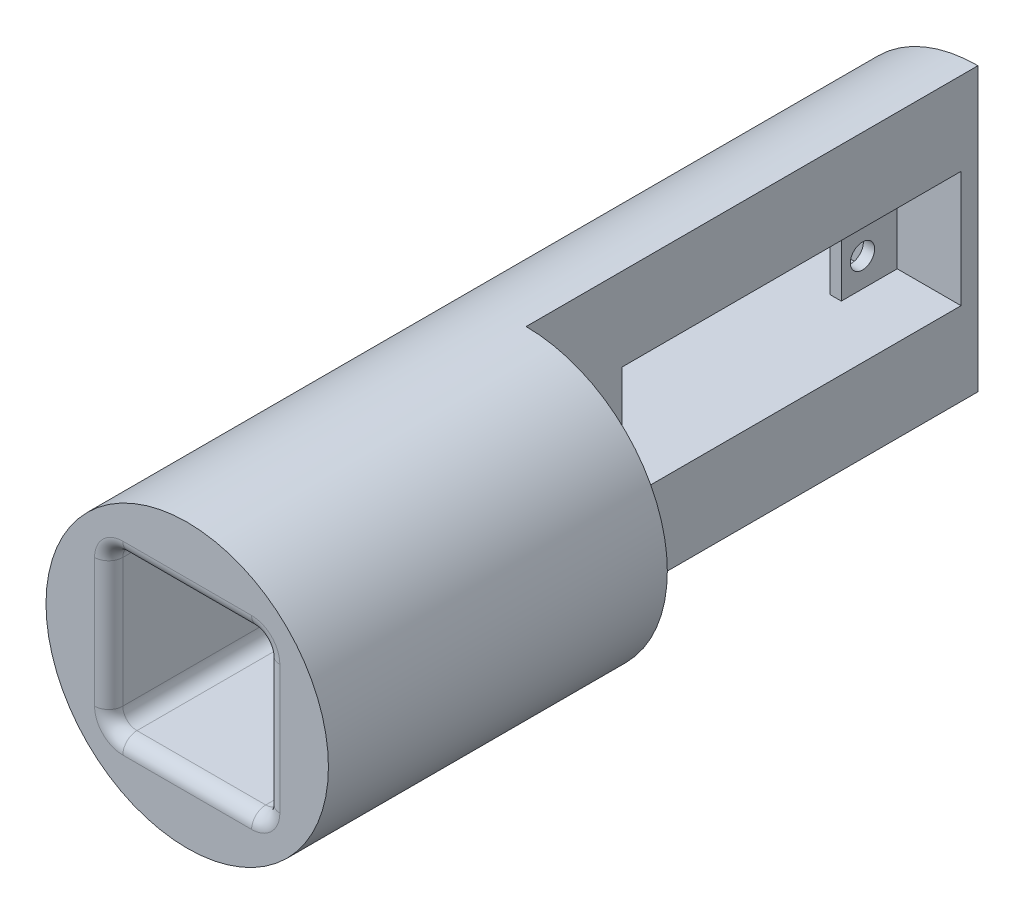
SolidWorks part; units mm, degrees
material "Custom Plastic"
ref_plane "Front Plane" through (0, 0, 0) normal (0, 0, 1) x (1, 0, 0)
ref_plane "Top Plane" through (0, 0, 0) normal (0, 1, 0) x (1, 0, 0)
ref_plane "Right Plane" through (0, 0, 0) normal (1, 0, 0) x (0, 0, -1)
sketch "Sketch1" plane through (0, 0, 0) normal (0, 0, 1) x (1, 0, 0)
  line L0 (-13.9, 13.9) -> (13.9, -13.9) construction
  line L1 (-13.9, 13.9) -> (13.9, 13.9)
  line L2 (-13.9, 13.9) -> (-13.9, -13.9)
  line L3 (-13.9, -13.9) -> (13.9, -13.9)
  line L4 (13.9, 13.9) -> (13.9, -13.9)
  circle A0 centre (0, 0) radius 25
  point P7 (0, 0)
  dimension "D2" = 50
  dimension "2.75" = 27.8
extrude "Boss-Extrude1" add sketch "Sketch1" along normal blind 55
sketch "Sketch2" plane through (0, 0, 0) normal (0, 0, -1) x (-1, 0, 0)
  circle A0 centre (0, 0) radius 25
  circle A1 centre (0, 0) radius 25
  circle A2 centre (0, 0) radius 25
  circle M2 centre (0, 0) radius 25
  line M3 (13.9, 13.9) -> (13.9, -13.9)
  line M4 (13.9, -13.9) -> (-13.9, -13.9)
  line M5 (-13.9, -13.9) -> (-13.9, 13.9)
  line M6 (-13.9, 13.9) -> (13.9, 13.9)
  dimension "D1" = 0
extrude "Boss-Extrude2" add sketch "Sketch2" along normal blind 5 contours M2 M6 M3 M4 M5 | M3 M6 M5 M4 region at (24.2929, 0, 0) region at (0, 0, 0)
sketch "Sketch3" plane through (0, 0, -5) normal (0, 0, -1) x (-1, 0, 0)
  line L1 (0, 25) -> (25, 25)
  line L2 (0, 25) -> (0, -25)
  line L3 (0, -25) -> (25, -25)
  line L4 (25, 25) -> (25, -25)
  circle A0 centre (0, 0) radius 25 construction
extrude "Boss-Extrude3" add sketch "Sketch3" along normal blind 80
ref_plane "Plane1" through (0, 0, -5) normal (0, 0, 1) x (1, 0, 0)
fillet "Fillet1" radius 2.5 4 edges at (-13.9, 13.9, 27.5) (13.9, 13.9, 27.5) (-13.9, -13.9, 27.5) (13.9, -13.9, 27.5)
fillet "Fillet2" radius 2.5 1 edges at (13.9, 0, 55) type face fillet first side face at (25, 0, 55) second side face at (13.9, 0, 27.5)
ref_plane "Plane2" through (-50, 0, 0) normal (-1, 0, 0) x (0, 0, 1)
sketch "Sketch18" plane through (0, 0, -5) normal (0, 0, 1) x (1, 0, 0)
  line L0 (0, -25) -> (-25, -25)
  line L1 (-25, 0) -> (-25, 25)
  line L2 (-25, -25) -> (0, -25)
  line L3 (-25, 0) -> (-25, -25)
  line L4 (-25, -25) -> (0, -25)
  line L5 (-25, 0) -> (-25, -25)
  line L6 (-25, 25) -> (0, 25)
  arc A1 (-25, 0) -> (0, -25) centre (0, 0) ccw
  arc A2 (-25, 0) -> (0, -25) centre (0, 0) ccw
  circle A3 centre (0, 0) radius 25
  circle A4 centre (0, 0) radius 25
  line M5 (-25, 25) -> (-25, 0)
  arc M6 (-25, 0) -> (0, 25) centre (0, 0) cw
  line M7 (0, 25) -> (-25, 25)
  dimension "D1" = 0
  dimension "D2" = 0
sketch "Sketch21" plane through (0, 0, 0) normal (1, 0, 0) x (0, 0, -1)
  line L0 (22, 10.3) -> (82, 10.3)
  line L1 (82, 10.3) -> (82, -10.3)
  line L2 (82, -10.3) -> (22, -10.3)
  line L3 (22, -10.3) -> (22, 10.3)
  line L6 (85, 25) -> (85, -25) construction
  line L7 (52, -10.3) -> (52, -25)
  line L8 (85, -25) -> (5, -25) construction
  line L9 (52, 10.3) -> (52, 25)
  line L10 (85, 25) -> (5, 25) construction
  dimension "D1" = 3
  dimension "D2" = 60
  dimension "D3" = 20.6
extrude "Cut-Extrude1" cut sketch "Sketch21" against normal blind 11.3 contours L3 L0 L1 L2
sketch "Sketch22" plane through (0, 0, 0) normal (1, 0, 0) x (0, 0, -1)
  line L0 (31.6, 10.3) -> (72.1, 10.3)
  line L1 (22, 10.3) -> (82, 10.3) construction
  line L2 (72.1, 10.3) -> (72.1, -10.3)
  line L4 (72.1, -10.3) -> (31.6, -10.3)
  line L5 (31.6, 10.3) -> (31.6, -10.3)
  line L6 (85, 25) -> (85, -25) construction
  line M9 (82, -10.3) -> (22, -10.3)
  line M11 (22, 10.3) -> (82, 10.3)
  dimension "D1" = 40.5
  dimension "D2" = 12.9
  dimension "D3" = 20.6
extrude "Cut-Extrude2" cut sketch "Sketch22" against normal through all contours L5 L2 M11 M9 region at (0, 0, -51.85)
extrude "Cut-Extrude3" cut sketch "Sketch18" against normal through all contours A2 L5 L0 | M7 M5 M6 region at (-19.4158, -19.4158, -5) region at (-19.4158, 19.4158, -5)
sketch "Sketch23" plane through (0, 0, 0) normal (1, 0, 0) x (0, 0, -1)
  line L0 (27.85, 5.25) -> (27.85, -5.25) construction
  line L1 (27.85, -5.25) -> (75.85, -5.25) construction
  line L2 (75.85, -5.25) -> (75.85, 5.25) construction
  line L3 (75.85, 5.25) -> (27.85, 5.25) construction
  circle A0 centre (75.85, 5.25) radius 2.15
  circle A1 centre (75.85, -5.25) radius 2.15
  circle A3 centre (27.85, 5.25) radius 2.15
  circle A4 centre (27.85, -5.25) radius 2.15
  dimension "D1" = 4.3
extrude "Cut-Extrude4" cut sketch "Sketch23" against normal through all contours A4 | A0 | A1 | A3 region at (0, 5.25, -75.85) region at (0, -5.25, -75.85) region at (0, -5.25, -27.85)
ref_plane "Plane3" through (0, 0, -51.85) normal (0, 0, -1) x (-1, 0, 0)
sketch "Sketch24" plane through (0, 0, -51.85) normal (0, 0, -1) x (-1, 0, 0)
  line L6 (13.3, 10.3) -> (13.3, -10.3)
  line L16 (22.7796, 10.3) -> (11.3, 10.3)
  line L17 (11.3, 10.3) -> (11.3, -10.3)
  line L18 (11.3, -10.3) -> (22.7796, -10.3)
  line L19 (22.7796, 10.3) -> (11.3, 10.3)
  line L20 (11.3, 10.3) -> (11.3, -10.3)
  line L21 (11.3, -10.3) -> (22.7796, -10.3)
  line L24 (0, 10.3) -> (0, -10.3)
  line L25 (0, -10.3) -> (11.3, -10.3)
  line L26 (11.3, -10.3) -> (11.3, 10.3)
  line L27 (11.3, 10.3) -> (0, 10.3)
  line L30 (11.3, -10.3) -> (11.3, 10.3)
  arc A1 (22.7796, -10.3) -> (22.7796, 10.3) centre (0, 0) ccw
  arc A5 (22.7796, -10.3) -> (22.7796, 10.3) centre (0, 0) ccw
  dimension "D1" = 0
  dimension "D2" = 2
  dimension "D4" = 20.6
  dimension "D3" = 0
extrude "Cut-Extrude7" cut sketch "Sketch24" against normal mid plane 55 contours L21 A5 L19 L6 region at (-18.8065, 0, -51.85)
sketch "Sketch25" plane through (0, 0, -24.35) normal (0, 0, -1) x (-1, 0, 0)
  line L3 (13.3, -10.3) -> (22.7796, -10.3)
  line L4 (22.7796, 10.3) -> (13.3, 10.3)
  line L5 (13.3, 10.3) -> (13.3, -10.3)
  line L6 (13.3, -10.3) -> (22.7796, -10.3)
  line L7 (22.7796, 10.3) -> (13.3, 10.3)
  line L8 (13.3, 10.3) -> (13.3, -10.3)
  arc A1 (22.7796, -10.3) -> (22.7796, 10.3) centre (0, 0) ccw
  arc A2 (22.7796, -10.3) -> (22.7796, 10.3) centre (0, 0) ccw
  dimension "D1" = 0
extrude "Cut-Extrude8" cut sketch "Sketch25" against normal blind 10 contours L6 A2 L7 L8
